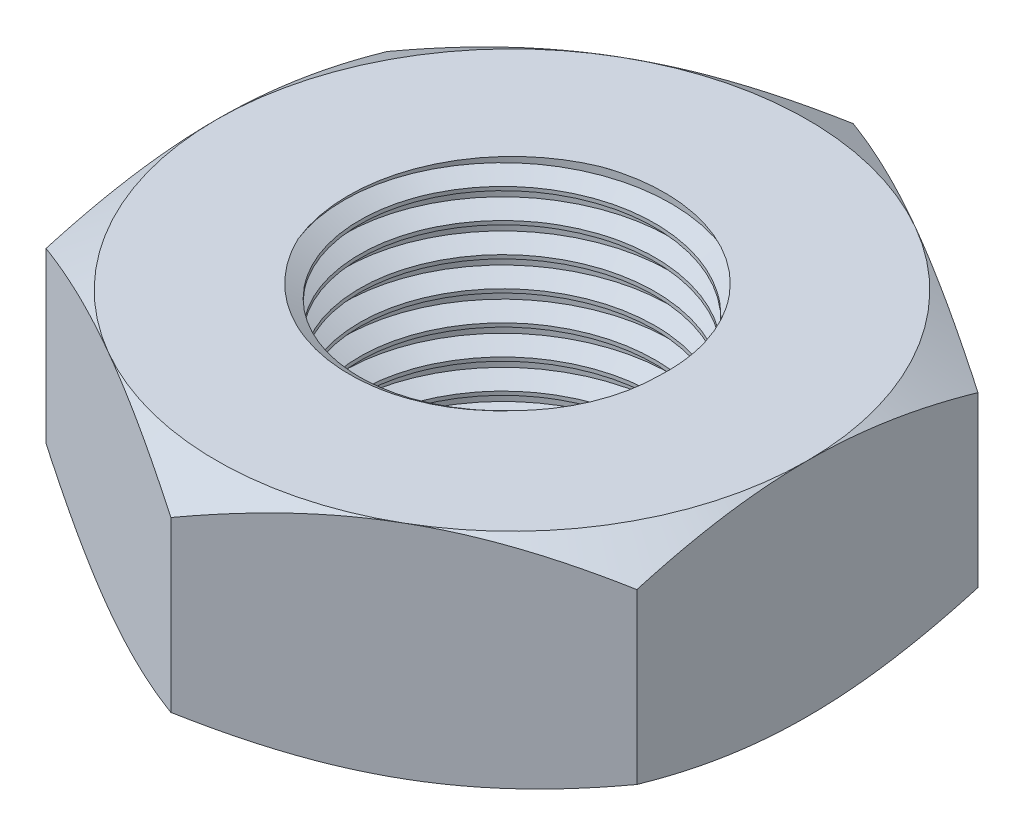
SolidWorks part; units mm, degrees
ref_plane "Front Plane" through (0, 0, 0) normal (0, 0, 1) x (1, 0, 0)
ref_plane "Top Plane" through (0, 0, 0) normal (0, 1, 0) x (1, 0, 0)
ref_plane "Right Plane" through (0, 0, 0) normal (1, 0, 0) x (0, 0, -1)
sketch "Sketch1" plane through (0, 0, 0) normal (0, 1, 0) x (1, 0, 0)
  line L1 (0, 23.094) -> (-20, 11.547)
  line L2 (-20, 11.547) -> (-20, -11.547)
  line L3 (-20, -11.547) -> (0, -23.094)
  line L4 (0, -23.094) -> (20, -11.547)
  line L5 (20, -11.547) -> (20, 11.547)
  line L6 (20, 11.547) -> (0, 23.094)
  circle A0 centre (0, 0) radius 20 construction
  circle A1 centre (0, 0) radius 10
  dimension "D2" = 20
  dimension "D1" = 40
extrude "Boss-Extrude1" add sketch "Sketch1" along normal mid plane 15
thread "Thread1" pitch 2 method cut trim with start face yes trim with end face yes profile "Thread Profile1" start angle 0, offset 5, length 27, pitch 2, diameter 20
ref_plane "Plane1" through (-10, 12.5, 0) normal (0, 0, -1) x (1, 0, 0)
sketch "Thread Profile1" plane through (-10, 12.5, 0) normal (0, 0, -1) x (1, 0, 0)
  line L0 (0, 0) -> (0, 2) construction
  line L11 (0, 0) -> (0, 1.75)
  line L12 (0, 1.75) -> (-1.0825, 1.125)
  line L13 (-1.0825, 1.125) -> (-1.0825, 0.625)
  line L15 (-1.0825, 0.625) -> (0, 0)
  line L17 (-1.0825, 0.875) -> (0, 0.875) construction
  point P2 (0, 0)
  dimension "Pitch" = 2
  dimension "Profile_Angle" = 60
  dimension "Profile_Land" = 0.5
  dimension "Profile_Height" = 1.0825
sketch "Sketch5" plane through (0, 7.5, 0) normal (0, 1, 0) x (1, 0, 0)
  line L0 (0, 23.094) -> (-20, 11.547) construction
  circle A0 centre (0, 0) radius 20
extrude "Cut-Extrude1" cut sketch "Sketch5" against normal through all both draft 60 and the other way through all flip side to cut
mirror "Mirror1" about plane through (0, 0, 0) normal (0, 1, 0) of "Cut-Extrude1"
